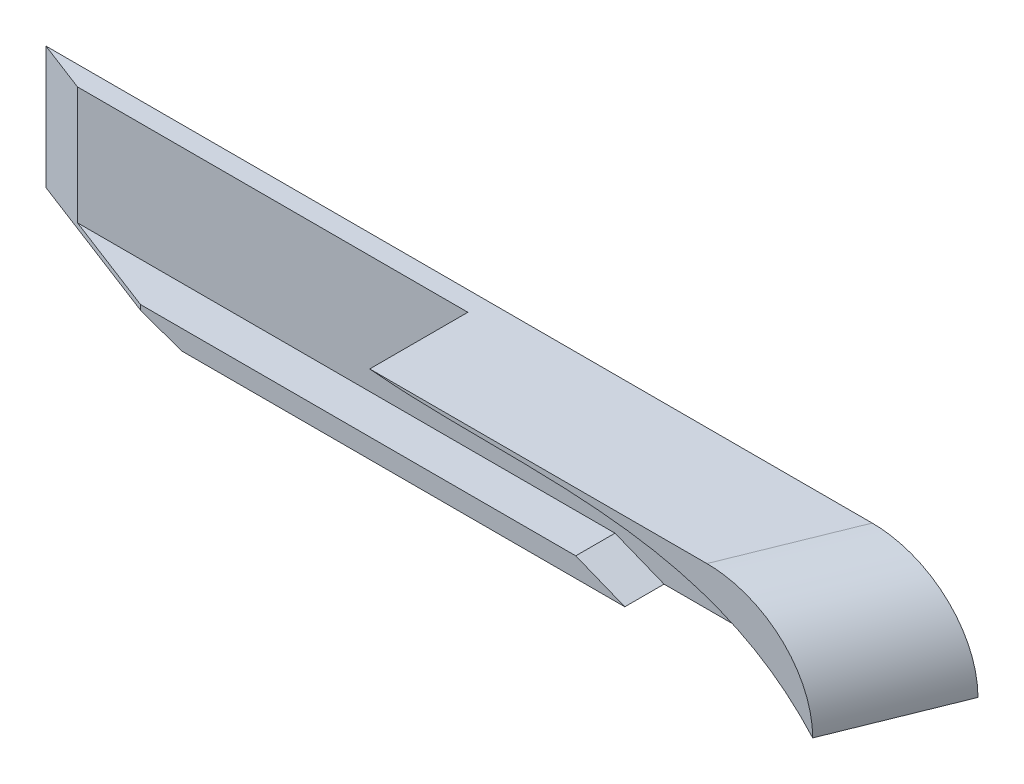
SolidWorks part; units mm, degrees
ref_plane "Płaszczyzna przednia" through (0, 0, 0) normal (0, 0, 1) x (1, 0, 0)
ref_plane "Płaszczyzna górna" through (0, 0, 0) normal (0, 1, 0) x (1, 0, 0)
ref_plane "Płaszczyzna prawa" through (0, 0, 0) normal (1, 0, 0) x (0, 0, -1)
sketch "Sketch1" plane through (0, 0, 0) normal (0, 0, 1) x (1, 0, 0)
  line L1 (-52.0588, 11.9069) -> (32.9412, 11.9069)
  line L2 (-52.0588, 11.9069) -> (-52.0588, -2.0931)
  line L3 (-52.0588, -2.0931) -> (32.9412, -2.0931)
  line L4 (32.9412, 11.9069) -> (32.9412, -2.0931)
  dimension "D1" = 14
  dimension "D2" = 85
extrude "Boss-Extrude1" add sketch "Sketch1" along normal blind 2
sketch "Sketch2" plane through (0, 0, 0) normal (0, 0, 1) x (1, 0, 0)
  line L0 (32.9412, -2.0931) -> (32.9412, 11.9069) construction
  line L1 (-52.0588, -2.0931) -> (32.9412, -2.0931)
  line L2 (-52.0588, -2.0931) -> (-52.0588, -0.0931)
  line L3 (-52.0588, -0.0931) -> (32.9412, -0.0931)
  line L4 (32.9412, -2.0931) -> (32.9412, -0.0931)
  dimension "D1" = 2
extrude "Boss-Extrude2" add sketch "Sketch2" along normal blind 6
sketch "Sketch3" plane through (0, 0, 6) normal (0, 0, 1) x (1, 0, 0)
  line L0 (32.9412, -0.0931) -> (7.9412, -0.0931)
  line L1 (32.9412, -0.0931) -> (-52.0588, -0.0931) construction
  line L2 (7.9412, -0.0931) -> (12.9412, -2.0931)
  line L3 (-52.0588, -2.0931) -> (32.9412, -2.0931) construction
  line L4 (12.9412, -2.0931) -> (32.9412, -2.0931)
  line L5 (32.9412, -2.0931) -> (32.9412, -0.0931)
  dimension "D1" = 20
  dimension "D2" = 25
extrude "Cut-Extrude1" cut sketch "Sketch3" against normal blind 4
sketch "Sketch4" plane through (0, 0, 0) normal (0, 0, -1) x (-1, 0, 0)
  line L0 (-32.9412, 11.9069) -> (-32.9412, 1.9069)
  line L1 (-32.9412, -2.0931) -> (-32.9412, 11.9069) construction
  line L2 (-32.9412, 1.9069) -> (-42.9412, 1.9069)
  line L3 (-32.9412, 11.9069) -> (-42.9412, 11.9069)
  line L4 (-42.9412, 11.9069) -> (-42.9412, 1.9069)
  dimension "D1" = 10
  dimension "D2" = 10
extrude "Boss-Extrude3" add sketch "Sketch4" against normal blind 2
sketch "Sketch5" plane through (0, -2.0931, 0) normal (0, -1, 0) x (1, 0, 0)
  line L4 (-52.0588, 0) -> (-36.4283, 6)
  line L5 (-52.0588, 6) -> (12.9412, 6) construction
  line L6 (-36.4283, 6) -> (-52.0588, 6)
  line L7 (-52.0588, 6) -> (-52.0588, 0)
  dimension "D1" = 21
extrude "Cut-Extrude2" cut sketch "Sketch5" against normal blind 20
chamfer "Chamfer1" distance 1.5 angle 45 1 edges at (-44.2436, -2.0931, 3)
sketch "Sketch6" plane through (42.9412, 0, 0) normal (1, 0, 0) x (0, 0, -1)
  line L1 (-2, 11.9069) -> (-12, 11.9069)
  line L2 (-2, 11.9069) -> (-2, 1.9069)
  line L3 (-2, 1.9069) -> (-12, 1.9069)
  line L4 (-12, 11.9069) -> (-12, 1.9069)
  dimension "D1" = 10
  dimension "D2" = 10
extrude "Boss-Extrude4" add sketch "Sketch6" against normal blind 50
sketch "Sketch7" plane through (0, 1.9069, 0) normal (0, -1, 0) x (1, 0, 0)
  line L0 (42.9412, 0) -> (38.0929, 12)
  line L1 (-7.0588, 12) -> (42.9412, 12) construction
  line L2 (38.0929, 12) -> (42.9412, 12)
  line L3 (42.9412, 12) -> (42.9412, 0)
  line L4 (42.9412, 0) -> (32.9412, 0) construction
  dimension "D1" = 68
extrude "Cut-Extrude3" cut sketch "Sketch7" against normal blind 50
fillet "Fillet1" radius 10 1 edges at (40.517, 11.9069, 6)
sketch "Sketch8" plane through (0, 0, 12) normal (0, 0, 1) x (1, 0, 0)
  line L0 (-7.0588, 11.9069) -> (27.3075, 11.9069) construction
  line L1 (-7.0588, 11.9069) -> (-7.0588, 1.9069) construction
  line L2 (-7.0588, 1.9069) -> (-7.0588, 11.9069) construction
  line L3 (-7.0588, 11.9069) -> (-7.0588, 1.9069)
  line L4 (-7.0588, 1.9069) -> (38.0929, 1.9069)
  spline S0 degree 3 poles (-7.0588, 11.9069) (7.5974, 10.4162) (26.9852, 14.4168) (38.0929, 1.9069) knots 0 0 0 0 1 1 1 1
  dimension "D1" = 0.5
  dimension "D2" = 17
  dimension "D3" = 4.5
  dimension "D4" = 38
extrude "Cut-Extrude4" cut sketch "Sketch8" against normal blind 10
